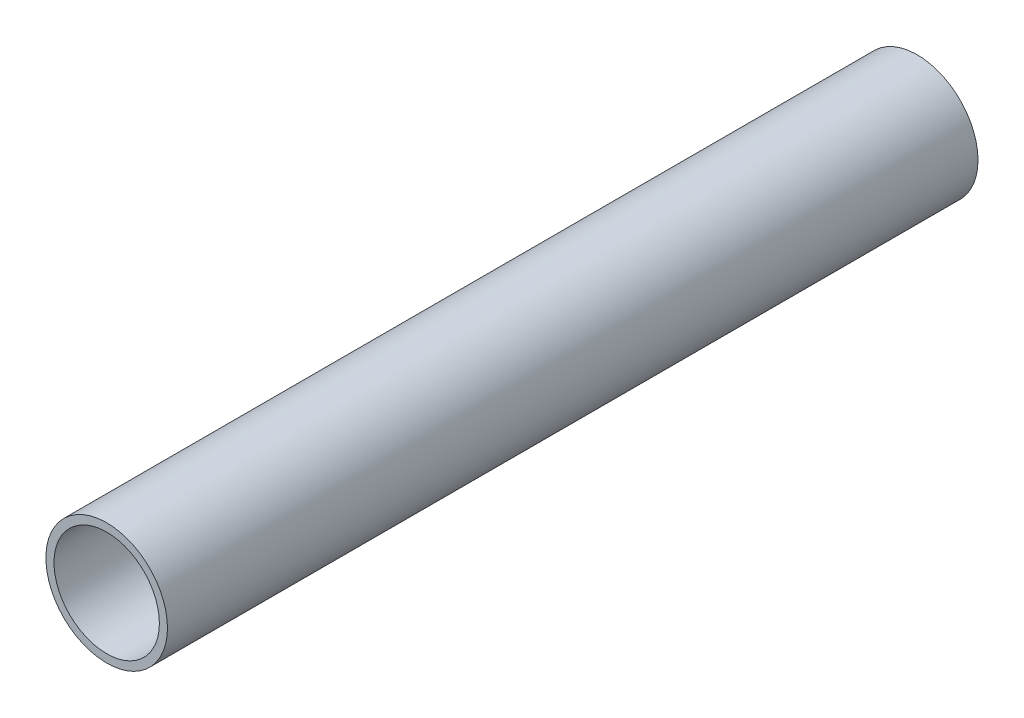
SolidWorks part; units mm, degrees
ref_plane "Front Plane" through (0, 0, 0) normal (0, 0, 1) x (1, 0, 0)
ref_plane "Top Plane" through (0, 0, 0) normal (0, 1, 0) x (1, 0, 0)
ref_plane "Right Plane" through (0, 0, 0) normal (1, 0, 0) x (0, 0, -1)
sketch "Sketch1" plane through (0, 0, 0) normal (0, 0, 1) x (1, 0, 0)
  circle A0 centre (0, 0) radius 19.05
  dimension "D1" = 38.1
extrude "Extrude-Thin1" add sketch "Sketch1" against normal blind 254 thin thin type one direction reverse wall 2.54
